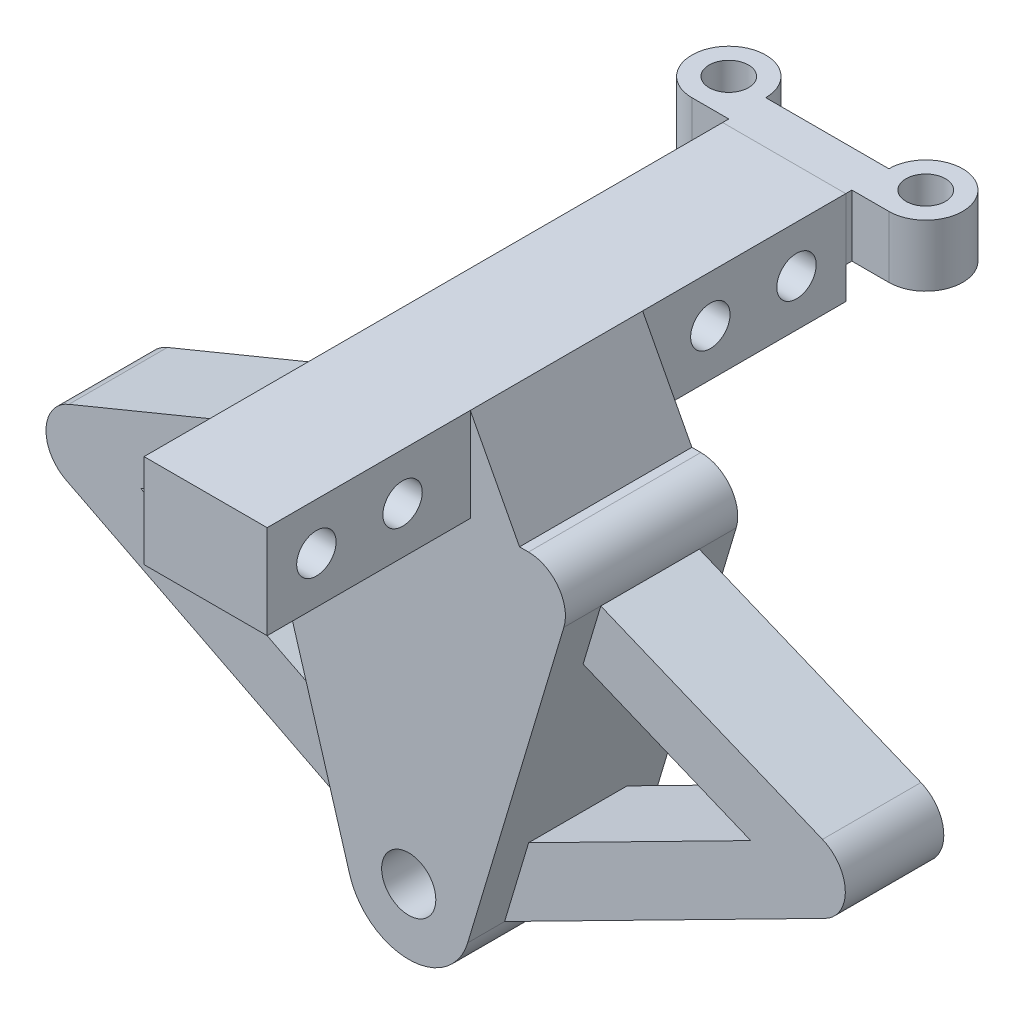
SolidWorks part; units mm, degrees
ref_plane "前视基准面" through (0, 0, 0) normal (0, 0, 1) x (1, 0, 0)
ref_plane "上视基准面" through (0, 0, 0) normal (0, 1, 0) x (1, 0, 0)
ref_plane "右视基准面" through (0, 0, 0) normal (1, 0, 0) x (0, 0, -1)
sketch "草图1" plane through (0, 0, 0) normal (1, 0, 0) x (0, 0, -1)
  line L0 (0, 0) -> (-23.5, 0) construction
  line L1 (23.5, -3.8) -> (-23.5, -3.8)
  line L2 (23.5, -3.8) -> (23.5, 3.8)
  line L3 (23.5, 3.8) -> (-23.5, 3.8)
  line L4 (-23.5, -3.8) -> (-23.5, 3.8)
  line L5 (23.5, -3.8) -> (-23.5, 3.8) construction
  line L6 (23.5, 3.8) -> (-23.5, -3.8) construction
  line L7 (0, 0) -> (0, -7.5593) construction
  circle A0 centre (-19.5, 0) radius 1.6
  circle A1 centre (-12.5, 0) radius 1.6
  circle A4 centre (12.5, 0) radius 1.6
  circle A5 centre (19.5, 0) radius 1.6
  point P0 (0, 0)
  dimension "D1" = 47
  dimension "D2" = 7.6
  dimension "D3" = 7
  dimension "D4" = 12.5
extrude "凸台-拉伸1" add sketch "草图1" along normal mid plane 10
sketch "草图4" plane through (0, 0, 0) normal (0, 0, 1) x (1, 0, 0)
  line L0 (0, 0) -> (0, 7.8238) construction
  line L2 (5, 3.8) -> (5, -3.8)
  line L3 (5, -3.8) -> (9, -3.8)
  line L6 (-5, -3.8) -> (-9, -3.8)
  line L7 (-5, 3.8) -> (-5, -3.8)
  line L9 (-5, 3.8) -> (-9, -3.8)
  line L10 (5, 3.8) -> (9, -3.8)
extrude "凸台-拉伸3" add sketch "草图4" along normal mid plane 14
sketch "草图3" plane through (0, 0, 0) normal (0, 0, 1) x (1, 0, 0)
  line L0 (0, -3.8) -> (0, -9.8882) construction
  line L2 (0, -3.8) -> (-13.7569, -3.8)
  line L3 (5, -3.8) -> (-5, -3.8) construction
  line L4 (-13.7569, -3.8) -> (0, -49.7667)
  line L5 (0, -49.7667) -> (13.7569, -3.8)
  line L6 (13.7569, -3.8) -> (0, -3.8)
  circle A0 centre (0, -32.0203) radius 2.2
extrude "凸台-拉伸2" add sketch "草图3" along normal mid plane 14
fillet "圆角1" radius 5 1 edges at (0, -49.7667, 0)
fillet "圆角2" radius 3 2 edges at (-13.7569, -3.8, 0) (13.7569, -3.8, 0)
sketch "草图5" plane through (0, 0, 0) normal (0, 0, 1) x (1, 0, 0)
  line L0 (-12.6016, -7.6601) -> (-36.6477, -17.5625)
  line L1 (-36.6477, -17.5625) -> (-4.7901, -33.7614)
  line L2 (-12.6016, -7.6601) -> (-11.1642, -12.4632)
  line L3 (-24.7828, -18.0714) -> (-11.1642, -12.4632)
  line L4 (-24.7828, -18.0714) -> (-6.7401, -27.2457)
  line L5 (-6.7401, -27.2457) -> (-4.7901, -33.7614)
  line L6 (-12.6016, -7.6601) -> (-4.7901, -33.7614) construction
extrude "凸台-拉伸4" add sketch "草图5" along normal mid plane 8
fillet "圆角3" radius 3 1 edges at (-36.6477, -17.5625, 0)
mirror "镜向1" about plane through (0, 0, 0) normal (1, 0, 0) of "圆角3", "凸台-拉伸4"
sketch "草图6" plane through (0, 3.8, 0) normal (0, 1, 0) x (1, 0, 0)
  line L0 (-5, 23.5) -> (-5, 24)
  line L1 (-5, 24) -> (-8, 24)
  line L11 (5, 23.5) -> (-5, 23.5)
  line L12 (0, 23.5) -> (0, 32.0606) construction
  line L13 (-5, 27) -> (5, 27)
  line L15 (5, 24) -> (8, 24)
  line L16 (5, 23.5) -> (5, 24)
  circle A0 centre (-8, 27) radius 1.6
  arc A2 (-5, 27) -> (-8, 24) centre (-8, 27) ccw
  arc A3 (5, 27) -> (8, 24) centre (8, 27) cw
  circle A4 centre (8, 27) radius 1.6
  dimension "D2" = 3
  dimension "D1" = 8
  dimension "D3" = 0.5
extrude "凸台-拉伸5" add sketch "草图6" against normal blind 5 separate body
